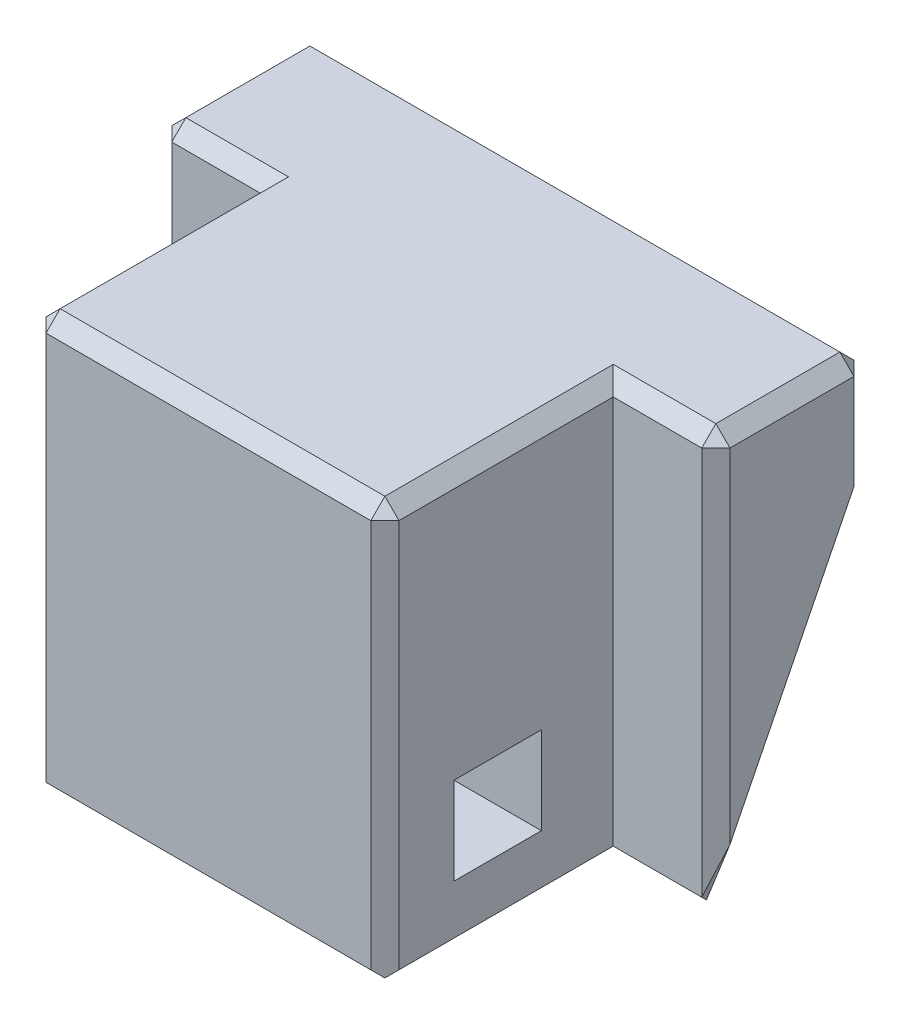
SolidWorks part; units mm, degrees
note: The reader was unsure of these and kept them because the rebuilt part matched: shared geometry of "Sketch4<5>".
ref_plane "Front Plane" through (0, 0, 0) normal (0, 0, 1) x (1, 0, 0)
ref_plane "Top Plane" through (0, 0, 0) normal (0, 1, 0) x (1, 0, 0)
ref_plane "Right Plane" through (0, 0, 0) normal (1, 0, 0) x (0, 0, -1)
ref_plane "Plane1" through (25.9401, 0, 0) normal (1, 0, 0) x (0, 0, -1)
sketch "Sketch4" plane through (25.9401, 0, 0) normal (1, 0, 0) x (0, 0, -1)
  line L1 (-29.6022, -20.126) -> (-32.8134, -26.5483) construction
  line L4 (-28.7936, -39.626) -> (-28.7936, -20.626) construction
  line L5 (-49.7936, 153.574) -> (-25.4048, 153.574) construction
  line L6 (-49.7936, 153.574) -> (-25.4048, 153.574) construction
  line L15 (-34.7936, 138.574) -> (-42.7936, 138.574) construction
  line L16 (-42.7936, 138.774) -> (-34.6936, 138.774)
  line L17 (-42.7936, -16.426) -> (-42.7936, 143.574) construction
  line L18 (-34.7936, 153.574) -> (-34.7936, 133.574) construction
  line L19 (-34.6936, 138.774) -> (-29.2936, 149.574)
  line L20 (-29.2936, 149.574) -> (-29.2936, 153.574)
  line L22 (-29.2936, 153.574) -> (-42.7936, 153.574)
  line L23 (-42.7936, 153.574) -> (-42.7936, 138.774)
  line L24 (-40.3436, 144.124) -> (-40.3436, 141.024)
  line L25 (-40.3436, 141.024) -> (-37.2436, 141.024)
  line L26 (-37.2436, 141.024) -> (-37.2436, 144.124)
  line L27 (-37.2436, 144.124) -> (-40.3436, 144.124)
  line L28 (-34.6936, 138.774) -> (-34.6936, 153.574)
  point P0 (-37.8436, 141.624)
  dimension "D1" = 0.2
  dimension "D2" = 0.5
  dimension "D3" = 0.1
extrude "Boss-Extrude1" add sketch "Sketch4" along normal offset from surface 0.1 and the other way offset from surface (6.2604 mm away) 0.1 contours L16 L28 L22 L23 L27 L26 L25 L24
extrude "Boss-Extrude2" add sketch "Sketch4<5>" along normal offset from surface 0.1 and the other way offset from surface (9.9 mm away) 0.1 contours L28 L19 L20 L22
sketch "Sketch4<5>" plane through (25.9401, 0, 0) normal (1, 0, 0) x (0, 0, -1) same geometry as "Sketch4"
chamfer "Chamfer1" distance 0.5 angle 45 19 edges at (17.8599, 138.774, 34.6936) (34.0203, 138.774, 34.6936) (32.2005, 153.574, 38.7436) (19.6797, 153.574, 38.7436) (17.8599, 153.574, 34.6936) (16.0401, 153.574, 31.9936) (16.0401, 146.174, 34.6936) (16.0401, 144.174, 31.9936) (16.0401, 151.574, 29.2936) (25.9401, 153.574, 29.2936) (35.8401, 153.574, 31.9936) (35.8401, 151.574, 29.2936) (35.8401, 144.174, 31.9936) (35.8401, 146.174, 34.6936) (34.0203, 153.574, 34.6936) (25.9401, 138.774, 42.7936) (32.2005, 146.174, 42.7936) (19.6797, 146.174, 42.7936) (25.9401, 153.574, 42.7936)
chamfer "Chamfer2" distance 0.5 angle 45 2 edges at (32.2005, 138.774, 38.4936) (19.6797, 138.774, 38.4936)
